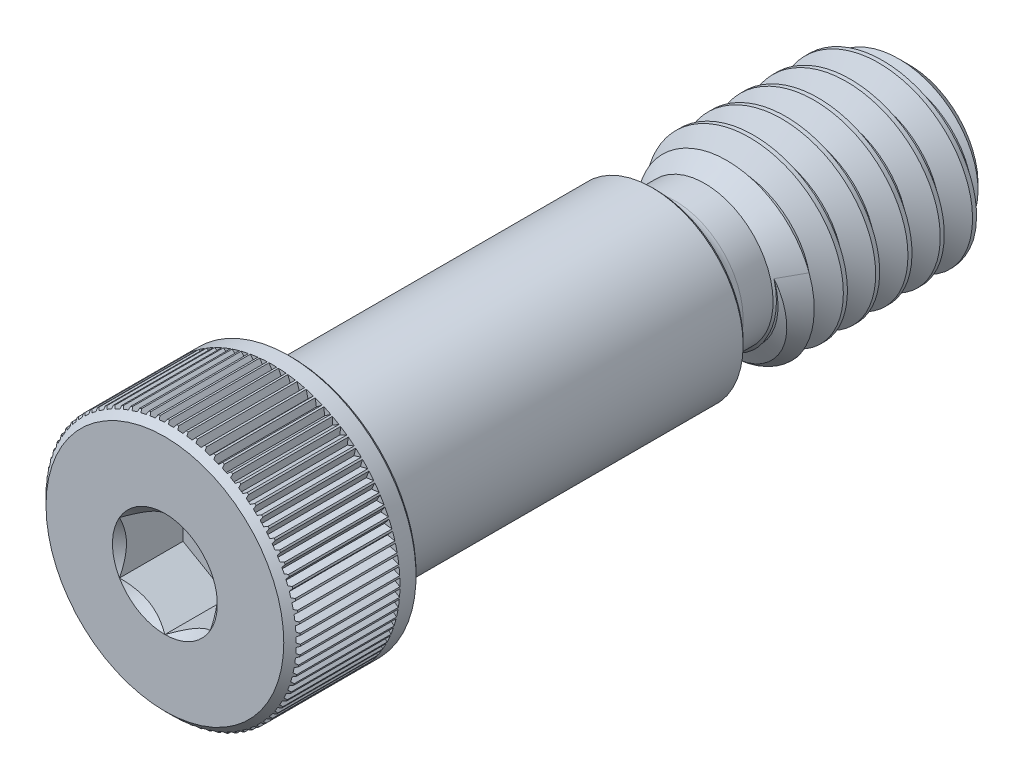
SolidWorks part; units mm, degrees
ref_plane "Front Plane" through (0, 0, 0) normal (0, 0, 1) x (1, 0, 0)
ref_plane "Top Plane" through (0, 0, 0) normal (0, 1, 0) x (1, 0, 0)
ref_plane "Right Plane" through (0, 0, 0) normal (1, 0, 0) x (0, 0, -1)
sketch "Sketch1" plane through (0, 0, 0) normal (1, 0, 0) x (0, 0, -1)
  line L0 (0, 0) -> (11.1125, 0) construction
  line L1 (0, 0) -> (-15.875, 0) construction
  line L2 (11.1125, 3.9751) -> (11.1125, -3.9751) construction
  line L3 (11.0243, 4.1279) -> (12.4354, 4.1279) construction
  line L4 (12.4354, 4.1279) -> (11.7299, 2.9058) construction
  line L5 (11.7299, 2.9058) -> (11.0243, 4.1279) construction
  line L6 (11.0684, 4.0515) -> (12.3913, 4.0515) construction
  line L7 (11.1125, 3.9751) -> (12.3472, 3.9751) construction
  line L8 (11.6417, 3.0586) -> (11.8181, 3.0586) construction
  line L9 (11.7299, 3.0586) -> (11.7299, 2.9058) construction
  line L10 (11.7299, 3.9751) -> (11.7299, 4.1279) construction
  line L11 (0, 3.9751) -> (0, -3.9751) construction
  line L12 (-15.875, 0) -> (-21.4312, 0) construction
  line L13 (-21.4313, 5.5562) -> (-21.4312, -5.5563) construction
  line L14 (-15.875, 5.5562) -> (-15.875, -5.5562) construction
  point P7 (11.1125, 0)
  point P12 (7.5847, -3.9751)
  point P19 (11.7299, 4.0515)
  point P23 (0, 0)
  point P27 (-21.4312, 0)
  point P29 (-15.875, 0)
  point P30 (-21.4312, -1.9844)
  point P31 (-21.4312, 1.9844)
  point P32 (11.1125, 3.9688)
  point P33 (-18.6531, 0)
  point P34 (11.1125, -3.9688)
  dimension "Screw Size Decimal Equivalent" = 7.9502
  dimension "D1" = 60
  dimension "Pitch" = 1.4111
  dimension "D2" = 0.1764
  dimension "Thread Length" = 11.1125
  dimension "D3" = 3.5278
  dimension "Head Diameter" = 11.1125
  dimension "Head Height" = 5.5562
  dimension "Shoulder Length" = 15.875
  dimension "Drive Size" = 3.9688
  dimension "D4" = 2.7781
  dimension "Shoulder Diameter" = 7.9375
sketch "Sketch2" plane through (0, 0, 0) normal (1, 0, 0) x (0, 0, -1)
  line L0 (0, 3.9751) -> (3.1496, 3.9751) construction
  line L1 (3.1496, 3.9751) -> (2.159, 2.9845) construction
  line L2 (2.159, 2.9845) -> (0, 2.9845) construction
  line L3 (0, 0) -> (11.1125, 0) construction
  line L4 (0, 0) -> (11.1125, 0) construction
  line L6 (0, 3.9751) -> (0, -3.9751) construction
  dimension "Thread Neck (Undercut) Width/Length" = 2.159
  dimension "D3" = 45
  dimension "Thread Neck (Undercut) Diameter" = 5.969
sketch "Sketch3" plane through (0, 0, 0) normal (1, 0, 0) x (0, 0, -1)
  line L0 (-21.4312, 5.1951) -> (-21.0701, 5.5562)
  line L1 (-21.4313, 5.5562) -> (-21.4312, -5.5563) construction
  line L2 (-21.0701, 5.5562) -> (-16.0139, 5.5562)
  line L3 (-16.0139, 5.5562) -> (-15.875, 5.4173)
  line L4 (-15.875, 5.4173) -> (-15.875, 3.9687)
  line L5 (-21.4312, 5.1951) -> (-21.4312, 0)
  line L6 (-21.4312, 0) -> (-15.3194, 0)
  line L7 (0, 0) -> (-15.875, 0) construction
  line L8 (-15.3194, 0) -> (-15.3194, 3.9687)
  line L9 (-15.3194, 3.9687) -> (-15.875, 3.9687)
  line L10 (0, 0) -> (-15.875, 0) construction
  dimension "D1" = 45
  dimension "D2" = 0.3612
  dimension "D3" = 45
  dimension "D4" = 0.1389
  dimension "D5" = 0.5556
  dimension "D6" = 7.9375
revolve "Revolve1" add sketch "Sketch3" angle 360 about L6
fillet "Fillet1" radius 0.1588 1 edges at (0, -3.9687, 15.875)
sketch "Sketch4" plane through (0, 0, 0) normal (1, 0, 0) x (0, 0, -1)
  line L0 (-15.3194, 3.9751) -> (-0.1389, 3.9751)
  line L1 (0, 3.8362) -> (0, 0)
  line L2 (0, 0) -> (-15.3194, 0)
  line L3 (-15.3194, 0) -> (-15.3194, 3.9751)
  line L4 (-0.1389, 3.9751) -> (0, 3.8362)
  dimension "D1" = 45
  dimension "D2" = 0.1389
revolve "Revolve2" add sketch "Sketch4" angle 360 about L2
sketch "Sketch5" plane through (0, 0, 0) normal (1, 0, 0) x (0, 0, -1)
  line L0 (11.1125, 2.9873) -> (10.1247, 3.9751)
  line L1 (11.1125, 3.9751) -> (11.1125, -3.9751) construction
  line L2 (10.1247, 3.9751) -> (3.1496, 3.9751)
  line L3 (3.1496, 3.9751) -> (2.159, 2.9845)
  line L4 (2.159, 2.9845) -> (0.8517, 2.9845)
  line L5 (0, 3.8362) -> (0, 0)
  line L6 (0, 3.9751) -> (0, -3.9751) construction
  line L7 (0, 0) -> (11.1125, 0)
  line L8 (11.1125, 0) -> (11.1125, 2.9873)
  line L9 (2.159, 2.9845) -> (0, 2.9845) construction
  arc A1 (0.8517, 2.9845) -> (0, 3.8362) centre (0.8517, 3.8362) cw
  dimension "D1" = 45
  dimension "D2" = 0.9878
revolve "Revolve3" add sketch "Sketch5" angle 360 about L7
sketch "Sketch6" plane through (0, 0, 21.4312) normal (0, 0, 1) x (1, 0, 0)
  line L1 (-1.9844, 1.1457) -> (-1.9844, -1.1457)
  line L2 (-1.9844, -1.1457) -> (0, -2.2914)
  line L3 (0, -2.2914) -> (1.9844, -1.1457)
  line L4 (1.9844, -1.1457) -> (1.9844, 1.1457)
  line L5 (1.9844, 1.1457) -> (0, 2.2914)
  line L6 (0, 2.2914) -> (-1.9844, 1.1457)
  circle A0 centre (0, 0) radius 1.9844 construction
extrude "Cut-Extrude1" cut sketch "Sketch6" against normal up to vertex (2.7781 mm away) up to point (0, 0, 18.6531)
sketch "Sketch7" plane through (0, 0, 21.4312) normal (0, 0, 1) x (1, 0, 0)
  circle A0 centre (0, 0) radius 2.2914
extrude "Cut-Extrude2" cut sketch "Sketch7" against normal up to vertex (2.7781 mm away) draft 45 up to point (0, 0, 18.6531)
sketch "Sketch11" plane through (0, 0, 18.6531) normal (0, 0, 1) x (1, 0, 0)
  line L1 (-0.6945, 0.401) -> (-0.6945, -0.401)
  line L2 (-0.6945, -0.401) -> (0, -0.802)
  line L3 (0, -0.802) -> (0.6945, -0.401)
  line L4 (0.6945, -0.401) -> (0.6945, 0.401)
  line L5 (0.6945, 0.401) -> (0, 0.802)
  line L6 (0, 0.802) -> (-0.6945, 0.401)
  circle A0 centre (0, 0) radius 0.6945 construction
  dimension "D1" = 1.3891
extrude "Cut-Extrude4" cut sketch "Sketch11" against normal blind 1.3891 draft 45
sketch "Sketch12" plane through (0, 0, 0) normal (1, 0, 0) x (0, 0, -1)
  line L0 (-11.9062, 5.5562) -> (-11.9062, -5.5562) construction
  line L2 (-3.9688, 5.5562) -> (-3.9688, -5.5562) construction
  line L4 (-15.875, 5.5562) -> (-15.875, -5.5562) construction
  line L5 (0, 0) -> (-15.875, 0) construction
  line L7 (0, 3.9751) -> (0, -3.9751) construction
  point P3 (-11.9063, 0)
  point P6 (-3.9688, 0)
  dimension "D1" = 3.9688
  dimension "D2" = 3.9688
sketch "Sketch13" plane through (0, 0, 0) normal (0, 0, 1) x (1, 0, 0)
  circle A0 centre (0, 0) radius 5.5562 construction
sketch "Sketch8" plane through (0, 0, 0) normal (1, 0, 0) x (0, 0, -1)
  line L0 (11.0684, 4.0515) -> (12.3913, 4.0515)
  line L1 (12.3913, 4.0515) -> (11.8181, 3.0586)
  line L2 (11.8181, 3.0586) -> (11.6417, 3.0586)
  line L3 (11.6417, 3.0586) -> (11.0684, 4.0515)
sketch "Sketch9" plane through (0, 0, -11.1125) normal (0, 0, -1) x (-1, 0, 0)
  circle A0 centre (0, 0) radius 3.9751
curve "Helix/Spiral1" pitch 1.4111 height 11.1125 radius 3.9751 centre (0, 0, -11.1125) axis (0, 0, 1) start towards (0, 1, 0)
sweep "Cut-Sweep1" cut profiles "Sketch8" path "Helix/Spiral1"
ref_plane "Plane1" through (0, 0, 21.1604) normal (0, 0, 1) x (1, 0, 0)
sketch "Sketch10" plane through (0, 0, 21.1604) normal (0, 0, 1) x (1, 0, 0)
  line L0 (-0.1668, 5.5562) -> (0.1668, 5.5562)
  line L1 (-0.1668, 5.5562) -> (0, 5.2673)
  line L2 (0, 5.2673) -> (0.1668, 5.5562)
  line L3 (-0.1668, 5.5562) -> (0, 0) construction
  line L4 (0, 0) -> (0.1668, 5.5562) construction
  circle A0 centre (0, 0) radius 5.2673 construction
  point P7 (0, 5.5562)
  dimension "D1" = 0.2889
  dimension "D2" = 3.439
extrude "Cut-Extrude3" cut sketch "Sketch10" against normal blind 4.445
pattern_circular "CirPattern1" count 85 over 360 about axis through (0, 0, 15.875) along (0, 0, 1) of "Cut-Extrude3" reverse direction yes
equation "\"D2@Sketch1\"=\"Pitch@Sketch1\"/8"
equation "\"D3@Sketch1\"=\"Pitch@Sketch1\"*2.5"
equation "\"D4@Sketch1\"=\"Head Height@Sketch1\"*.5"
equation "\"D2@Sketch3\"=\"Head Height@Sketch1\" * .065"
equation "\"D4@Sketch3\" = \"Head Height@Sketch1\" * .025"
equation "\"D5@Sketch3\"=\"Head Height@Sketch1\"*.1"
equation "\"D1@Fillet1\"=\"Shoulder Diameter@Sketch1\"*.02"
equation "\"D2@Sketch5\"=\"Pitch@Sketch1\"*.7"
equation "\"D2@Sketch4\"=\"D4@Sketch3\""
equation "\"D3@Helix/Spiral1\"=\"Thread Length@Sketch1\""
equation "\"D4@Helix/Spiral1\"=\"Pitch@Sketch1\""
equation "\"D1@Sketch10\"=\"D2@Sketch3\"*.8"
equation "\"D1@Cut-Extrude3\"=\"Head Height@Sketch1\"*.8"
equation "\"D1@CirPattern1\"=(360/\"D2@Sketch10\")-20"
equation "\"D1@Plane1\"=\"D2@Sketch3\"*.75"
equation "\"D1@Sketch11\"=\"Drive Size@Sketch1\"*.35"
equation "\"D1@Cut-Extrude4\"=\"Head Height@Sketch1\"*.25"
equation "\"D1@Sketch12\"=\"Shoulder Length@Sketch1\"*.25"
equation "\"D2@Sketch12\"=\"D1@Sketch12\""
equation "\"D6@Sketch3\"=\"Shoulder Diameter@Sketch1\""
